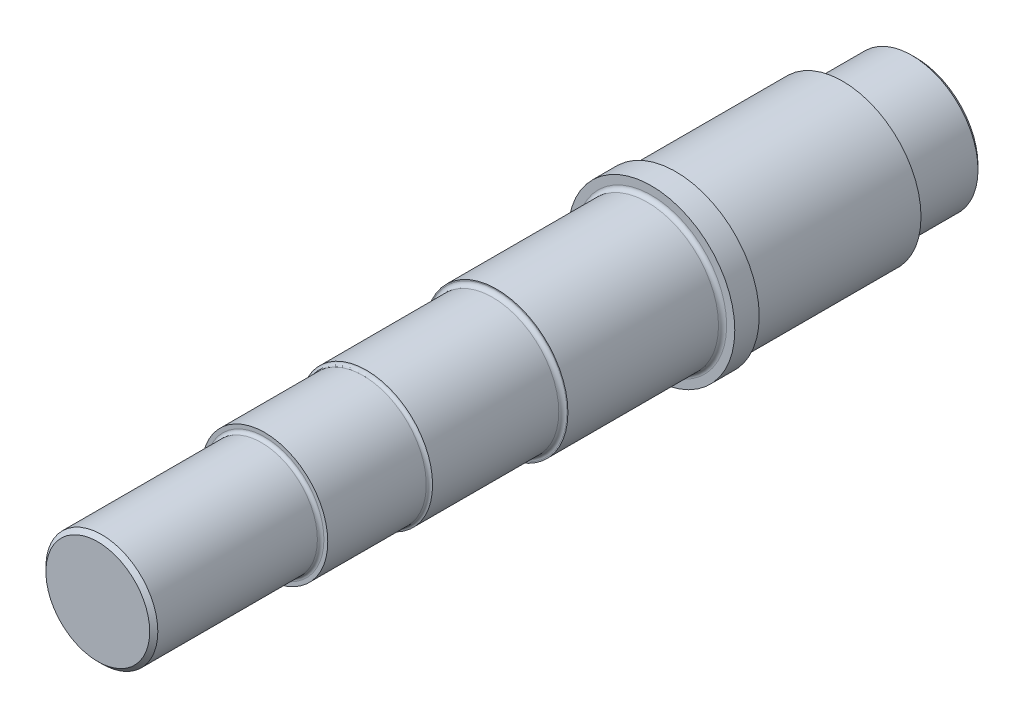
SolidWorks part; units mm, degrees
ref_plane "前视基准面" through (0, 0, 0) normal (0, 0, 1) x (1, 0, 0)
ref_plane "上视基准面" through (0, 0, 0) normal (0, 1, 0) x (1, 0, 0)
ref_plane "右视基准面" through (0, 0, 0) normal (1, 0, 0) x (0, 0, -1)
sketch "草图1" plane through (0, 0, 0) normal (0, 0, 1) x (1, 0, 0)
  circle A0 centre (0, 0) radius 32.5
  dimension "D1" = 65
extrude "凸台-拉伸1" add sketch "草图1" along normal blind 36
sketch "草图2" plane through (0, 0, 36) normal (0, 0, 1) x (1, 0, 0)
  circle A0 centre (0, 0) radius 38.5
  dimension "D1" = 77
extrude "凸台-拉伸2" add sketch "草图2" along normal blind 82
sketch "草图3" plane through (0, 0, 118) normal (0, 0, 1) x (1, 0, 0)
  circle A0 centre (0, 0) radius 41
  dimension "D1" = 82
extrude "凸台-拉伸3" add sketch "草图3" along normal blind 12
sketch "草图4" plane through (0, 0, 130) normal (0, 0, 1) x (1, 0, 0)
  circle A0 centre (0, 0) radius 35
  dimension "D1" = 70
extrude "凸台-拉伸4" add sketch "草图4" along normal blind 76
sketch "草图5" plane through (0, 0, 206) normal (0, 0, 1) x (1, 0, 0)
  circle A0 centre (0, 0) radius 32.5
  dimension "D1" = 65
extrude "凸台-拉伸5" add sketch "草图5" along normal blind 64
sketch "草图6" plane through (0, 0, 270) normal (0, 0, 1) x (1, 0, 0)
  circle A0 centre (0, 0) radius 31
  dimension "D1" = 62
extrude "凸台-拉伸6" add sketch "草图6" along normal blind 50
sketch "草图7" plane through (0, 0, 320) normal (0, 0, 1) x (1, 0, 0)
  circle A0 centre (0, 0) radius 27.5
  dimension "D1" = 55
extrude "凸台-拉伸7" add sketch "草图7" along normal blind 82
fillet "圆角1" radius 2 2 edges at (32.5, 0, 206) (35, 0, 130)
fillet "圆角2" radius 1.6 2 edges at (27.5, 0, 320) (31, 0, 270)
chamfer "倒角1" distance 2 angle 45 2 edges at (32.5, 0, 0) (27.5, 0, 402)
